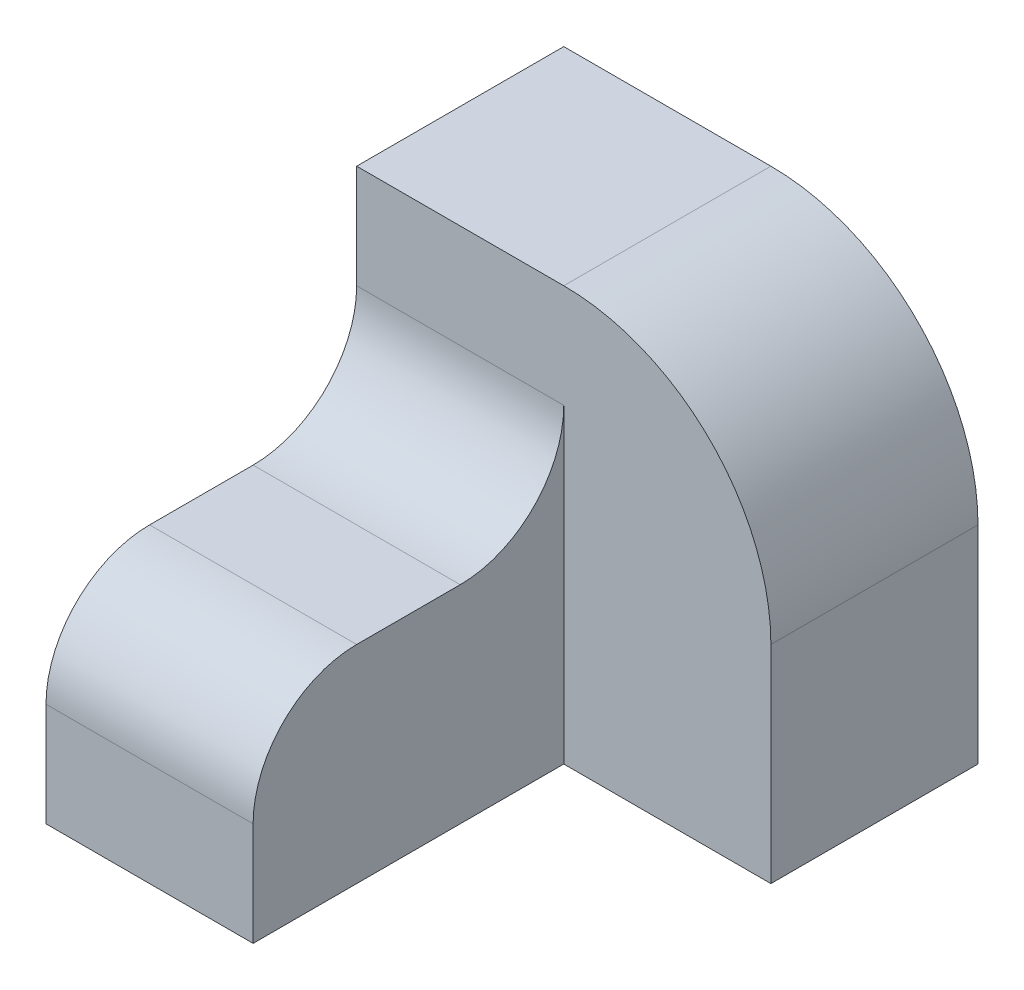
SolidWorks part; units mm, degrees
ref_plane "前基準面" through (0, 0, 0) normal (0, 0, 1) x (1, 0, 0)
ref_plane "上基準面" through (0, 0, 0) normal (0, 1, 0) x (1, 0, 0)
ref_plane "右基準面" through (0, 0, 0) normal (1, 0, 0) x (0, 0, -1)
sketch "草圖1" plane through (0, 0, 0) normal (0, 1, 0) x (1, 0, 0)
  line L0 (0, 0) -> (-40, 0)
  line L1 (-40, 0) -> (-40, 20)
  line L2 (-40, 20) -> (0, 20)
  line L3 (0, 20) -> (0, 0)
  line L4 (-20, 0) -> (-20, -30)
  line L5 (-20, -30) -> (-40, -30)
  line L6 (-40, -30) -> (-40, 0)
  dimension "D1" = 40
  dimension "D2" = 30
  dimension "D3" = 20
  dimension "D4" = 20
extrude "填料-伸長1" add sketch "草圖1" along normal blind 40 contours L3 L2 L1 L0 region at (-20, 0, -10)
extrude "填料-伸長2" add sketch "草圖1<3>" along normal blind 20 contours L6 L5 L4 L0 region at (-30, 0, 15)
sketch "草圖1<3>" plane through (0, 0, 0) normal (0, 1, 0) x (1, 0, 0) same geometry as "草圖1"
fillet "圓角1" radius 10 2 edges at (-30, 20, 0) (-30, 20, 30)
fillet "圓角2" radius 20 1 edges at (0, 40, -10)
